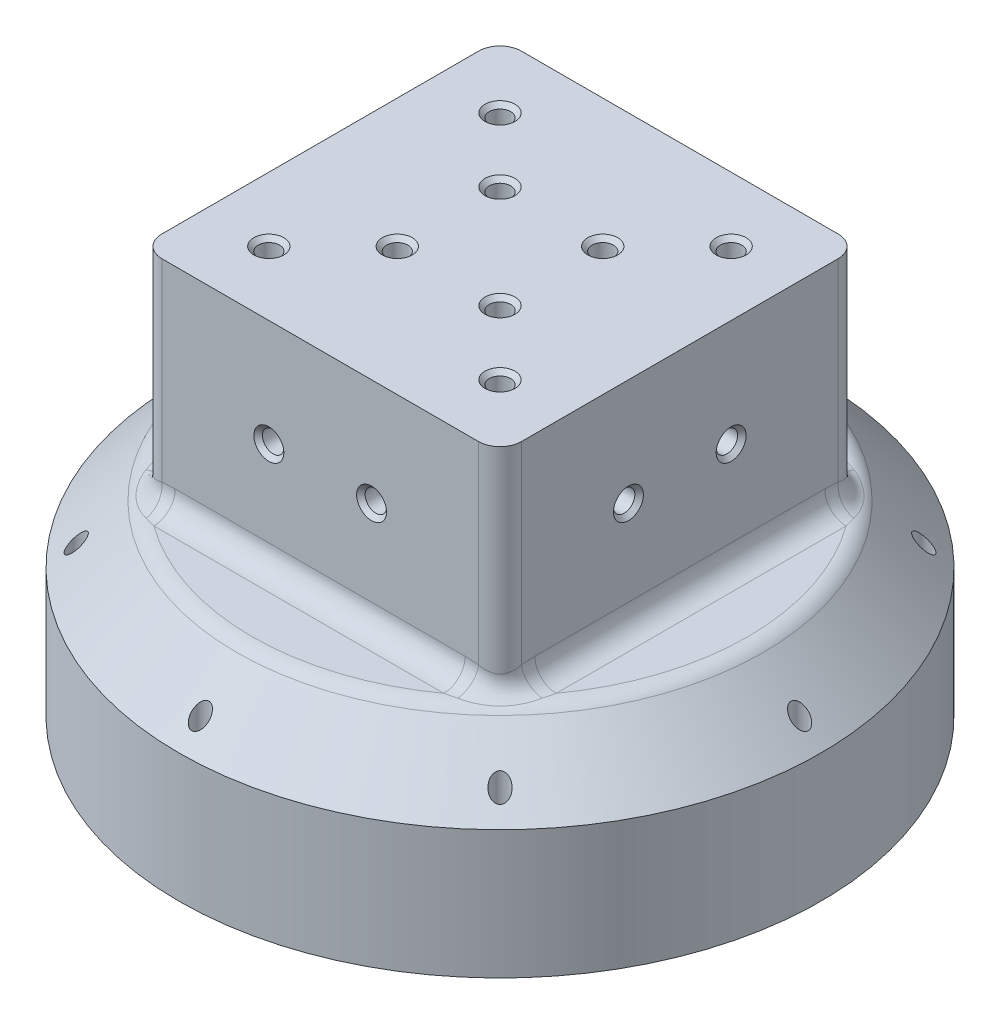
SolidWorks part; units mm, degrees
ref_plane "Front Plane" through (0, 0, 0) normal (0, 0, 1) x (1, 0, 0)
ref_plane "Top Plane" through (0, 0, 0) normal (0, 1, 0) x (1, 0, 0)
ref_plane "Right Plane" through (0, 0, 0) normal (1, 0, 0) x (0, 0, -1)
sketch "Sketch2" plane through (0, 0, 0) normal (1, 0, 0) x (0, 0, -1)
  line L0 (0, 0) -> (-75, 0)
  line L1 (-75, 0) -> (-75, 30)
  line L2 (-75, 30) -> (-60, 45)
  line L3 (-60, 45) -> (0, 45)
  line L4 (0, 45) -> (0, 0)
  dimension "D1" = 75
  dimension "D2" = 30
  dimension "D3" = 45
  dimension "D4" = 60
revolve "Revolve1" add sketch "Sketch2" angle 360 about L4
sketch "Sketch3" plane through (0, 45, 0) normal (0, 1, 0) x (1, 0, 0)
  line L1 (-42, 42) -> (42, 42)
  line L2 (-42, 42) -> (-42, -42)
  line L3 (-42, -42) -> (42, -42)
  line L4 (42, 42) -> (42, -42)
  line L5 (-42, 42) -> (42, -42) construction
  line L6 (-42, -42) -> (42, 42) construction
  point P0 (0, 0)
  dimension "D1" = 84
extrude "Boss-Extrude1" add sketch "Sketch3" along normal blind 50
fillet "Fillet10" radius 5 4 edges at (42, 70, 42) (-42, 70, 42) (-42, 70, -42) (42, 70, -42)
fillet "Fillet13" radius 5 1 edges at (0, 45, 60)
sketch "Sketch4" plane through (0, 0, 0) normal (0, -1, 0) x (1, 0, 0)
  circle A0 centre (0, 0) radius 70 construction
  circle A1 centre (0, 70) radius 2
  circle A2 centre (49.4975, 49.4975) radius 2
  circle A3 centre (70, 0) radius 2
  circle A4 centre (49.4975, -49.4975) radius 2
  circle A5 centre (0, -70) radius 2
  circle A6 centre (-49.4975, -49.4975) radius 2
  circle A7 centre (-70, 0) radius 2
  circle A8 centre (-49.4975, 49.4975) radius 2
  point P21 (0, 0)
  dimension "D1" = 140
  dimension "D2" = 4
  dimension "D4" = 70
  dimension "D3" = 8
extrude "Cut-Extrude1" cut sketch "Sketch4" against normal blind 50
sketch "Sketch5" plane through (0, 95, 0) normal (0, 1, 0) x (1, 0, 0)
  line L0 (-42, 37) -> (-42, -37) construction
  line L3 (40.5355, 40.5355) -> (-40.5355, -40.5355) construction
  line L4 (-40.5355, 40.5355) -> (40.5355, -40.5355) construction
  arc A0 (42, 37) -> (37, 42) centre (37, 37) ccw construction
  arc A1 (-42, -37) -> (-37, -42) centre (-37, -37) ccw construction
  arc A2 (-37, 42) -> (-42, 37) centre (-37, 37) ccw construction
  arc A3 (37, -42) -> (42, -37) centre (37, -37) ccw construction
  circle A4 centre (-12, 12) radius 2.5
  circle A5 centre (12, 12) radius 2.5
  circle A6 centre (12, -12) radius 2.5
  circle A7 centre (-12, -12) radius 2.5
  circle A8 centre (-27, 27) radius 2.5
  circle A9 centre (27, 27) radius 2.5
  circle A10 centre (27, -27) radius 2.5
  circle A11 centre (-27, -27) radius 2.5
  dimension "D1" = 5
  dimension "D3" = 5
  dimension "D2" = 30
  dimension "D4" = 15
extrude "Cut-Extrude7" cut sketch "Sketch5" against normal blind 10
sketch "Sketch6" plane through (0, 0, 42) normal (0, 0, 1) x (1, 0, 0)
  line L0 (-37, 95) -> (37, 95) construction
  line L2 (-42, 45) -> (-42, 95) construction
  line L3 (42, 95) -> (42, 45) construction
  circle A0 centre (-12, 70) radius 2.5
  circle A1 centre (12, 70) radius 2.5
  dimension "D1" = 5
  dimension "D2" = 30
  dimension "D3" = 30
  dimension "D4" = 25
extrude "Cut-Extrude8" cut sketch "Sketch6" against normal blind 10
sketch "Sketch7" plane through (0, 0, -42) normal (0, 0, -1) x (-1, 0, 0)
  line L0 (-42, 45) -> (-42, 95) construction
  line L1 (-42, 45) -> (-42, 95) construction
  line L2 (42, 95) -> (42, 45) construction
  line L3 (-37, 95) -> (37, 95) construction
  circle A0 centre (-12, 70) radius 2.5
  circle A1 centre (12, 70) radius 2.5
  dimension "D1" = 5
  dimension "D2" = 30
  dimension "D3" = 30
  dimension "D4" = 25
extrude "Cut-Extrude9" cut sketch "Sketch7" against normal blind 10
sketch "Sketch8" plane through (-42, 0, 0) normal (-1, 0, 0) x (0, 0, 1)
  line L1 (-42, 45) -> (-42, 95) construction
  line L2 (42, 95) -> (42, 45) construction
  line L3 (-37, 95) -> (37, 95) construction
  circle A0 centre (-12, 70) radius 2.5
  circle A1 centre (12, 70) radius 2.5
  dimension "D1" = 5
  dimension "D2" = 30
  dimension "D3" = 30
  dimension "D4" = 25
extrude "Cut-Extrude10" cut sketch "Sketch8" against normal blind 10
sketch "Sketch9" plane through (42, 0, 0) normal (1, 0, 0) x (0, 0, -1)
  line L1 (-42, 45) -> (-42, 95) construction
  line L2 (42, 95) -> (42, 45) construction
  line L3 (-37, 95) -> (37, 95) construction
  circle A0 centre (-12, 70) radius 2.5
  circle A1 centre (12, 70) radius 2.5
  dimension "D1" = 5
  dimension "D2" = 30
  dimension "D3" = 30
  dimension "D4" = 25
extrude "Cut-Extrude6" cut sketch "Sketch9" against normal blind 10
fillet "Fillet17" radius 5 8 edges at (-40.5355, 45, -40.5355) (0, 45, -42) (40.5355, 45, -40.5355) (42, 45, 0) (40.5355, 45, 40.5355) (0, 45, 42) (-40.5355, 45, 40.5355) (-42, 45, 0)
chamfer "Chamfer4" distance 1 angle 45 16 edges at (27, 95, 29.5) (27, 95, -24.5) (12, 95, -9.5) (12, 95, 14.5) (-27, 95, 29.5) (-12, 95, 14.5) (-12, 95, -9.5) (-27, 95, -24.5) (-14.5, 70, -42) (9.5, 70, -42) (42, 70, -14.5) (42, 70, 9.5) (-42, 70, -9.5) (-42, 70, 14.5) (14.5, 70, 42) (-9.5, 70, 42)
